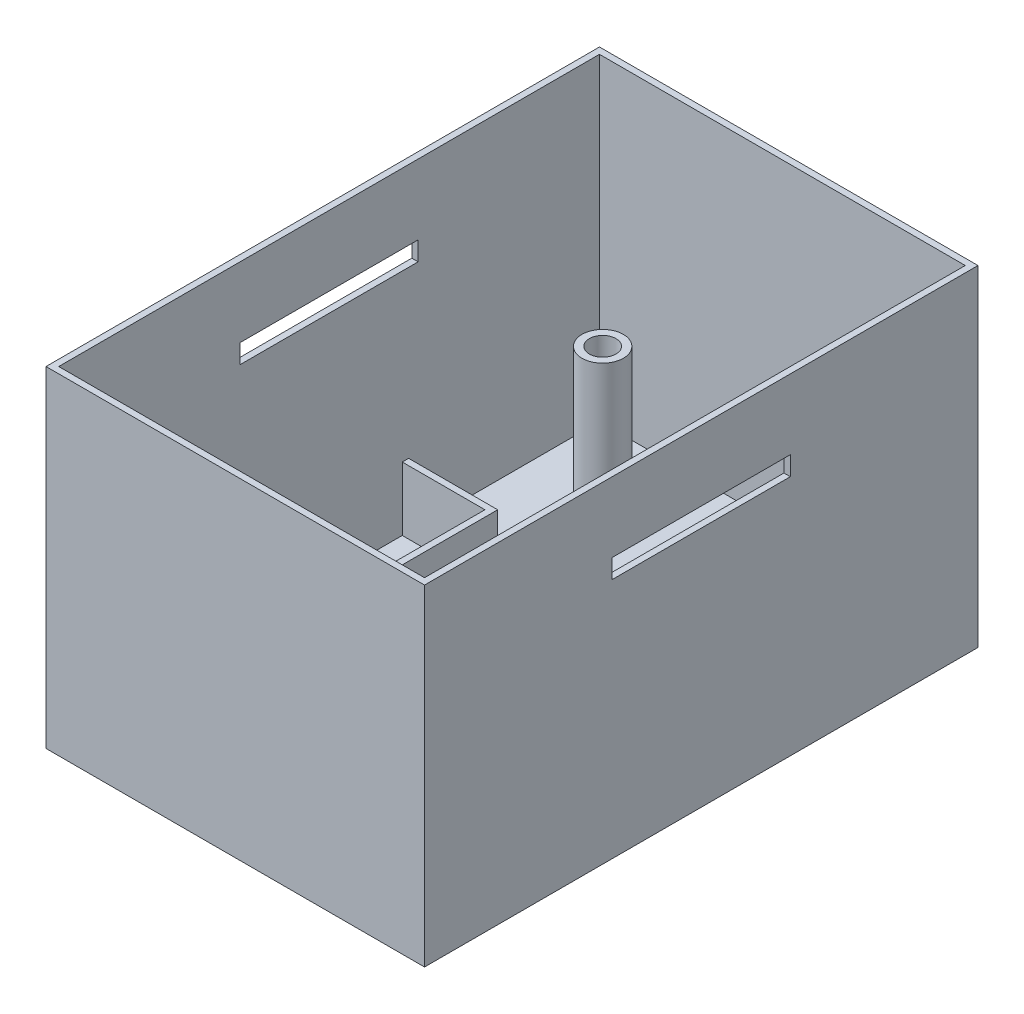
SolidWorks part; units mm, degrees
ref_plane "Alzado" through (0, 0, 0) normal (0, 0, 1) x (1, 0, 0)
ref_plane "Planta" through (0, 0, 0) normal (0, 1, 0) x (1, 0, 0)
ref_plane "Vista lateral" through (0, 0, 0) normal (1, 0, 0) x (0, 0, -1)
sketch "Croquis1" plane through (0, 0, 0) normal (0, 1, 0) x (1, 0, 0)
  line L0 (-19.25, 35.5) -> (-16.25, 35.5) construction
  line L1 (-19.25, -35.5) -> (19.25, -35.5) construction
  line L2 (-19.25, -35.5) -> (-19.25, 35.5) construction
  line L3 (-19.25, 35.5) -> (19.25, 35.5) construction
  line L4 (19.25, -35.5) -> (19.25, 35.5) construction
  line L5 (-19.25, -35.5) -> (19.25, 35.5) construction
  line L6 (-19.25, 35.5) -> (19.25, -35.5) construction
  line L7 (-28.75, -42.5) -> (28.75, -42.5)
  line L8 (-28.75, -42.5) -> (-28.75, 42.5)
  line L9 (-28.75, 42.5) -> (28.75, 42.5)
  line L10 (28.75, -42.5) -> (28.75, 42.5)
  line L11 (-28.75, -42.5) -> (28.75, 42.5) construction
  line L12 (-28.75, 42.5) -> (28.75, -42.5) construction
  line L13 (-19.25, 35.5) -> (-19.25, 32.5) construction
  line L14 (26.75, 41) -> (18.75, 41) construction
  line L15 (-26.75, -41) -> (26.75, -41) construction
  line L16 (-26.75, -41) -> (-26.75, 41) construction
  line L17 (0, 35.5) -> (0, -35.5) construction
  line L18 (0, -26.6301) -> (0, -35.5) construction
  line L19 (-28.75, -35.5) -> (-14.75, -35.5)
  line L20 (-14.75, -35.5) -> (-14.75, 12.5)
  line L21 (-14.75, 12.5) -> (-28.75, 12.5)
  line L22 (-15.75, -34.5) -> (-28.75, -34.5)
  line L23 (-15.75, -34.5) -> (-15.75, 11.5)
  line L24 (-15.75, 11.5) -> (-28.75, 11.5)
  line L25 (-29.75, -43.5) -> (-29.75, 43.5)
  line L26 (-29.75, 43.5) -> (29.75, 43.5)
  line L27 (29.75, -43.5) -> (29.75, 43.5)
  line L28 (-29.75, -43.5) -> (29.75, -43.5)
  line L29 (-28.75, -34.5) -> (-15.75, -34.5) construction
  line L30 (-26.75, 41) -> (26.75, 41) construction
  line L31 (26.75, -41) -> (26.75, 41) construction
  line L32 (-26.75, -41) -> (26.75, 41) construction
  line L33 (-26.75, 41) -> (26.75, -41) construction
  line L34 (18.75, 41) -> (18.75, 33) construction
  line L35 (26.75, -41) -> (19.75, -41) construction
  line L36 (19.75, -41) -> (19.75, -20) construction
  line L37 (-26.75, 41) -> (-18.75, 41) construction
  line L38 (-18.75, 41) -> (-18.75, 33) construction
  circle A2 centre (19.75, -20) radius 2.1
  circle A3 centre (19.75, -20) radius 3.25
  circle A4 centre (-18.75, 33) radius 2.1
  circle A5 centre (-18.75, 33) radius 3.25
  point P0 (0, 0)
  point P6 (0, 0)
  point P11 (0, 0)
  dimension "D7" = 8
  dimension "D8" = 8
  dimension "D13" = 8
  dimension "D14" = 4.2
  dimension "D15" = 21
  dimension "D19" = 4.2
  dimension "D20" = 6.5
  dimension "D22" = 6.5
  dimension "D1" = 71
  dimension "D2" = 38.5
  dimension "D3" = 57.5
  dimension "D4" = 85
  dimension "D5" = 53.5
  dimension "D6" = 82
  dimension "D9" = 8.8699
  dimension "D10" = 14
  dimension "D11" = 48
  dimension "D12" = 7
  dimension "D18" = 7
  dimension "D21" = 8
  dimension "D16" = 1
  dimension "D17" = 1
extrude "Saliente-Extruir1" add sketch "Croquis1" along normal blind 50 contours L25 L28 L27 L26 L10 L7 L8 L9 region at (-29.6446, 0, 0)
extrude "Saliente-Extruir2" add sketch "Croquis1<4>" along normal blind 10 contours L24 L23 L8 L19 L20 L21 region at (-28.25, 0, 35)
sketch "Croquis1<4>" plane through (0, 0, 0) normal (0, 1, 0) x (1, 0, 0) same geometry as "Croquis1"
extrude "Saliente-Extruir3" add sketch "Croquis1<5>" along normal blind 20 separate body contours A4 | A2 | A3 | A5 region at (19.75, 0, 20) region at (-18.75, 0, -33)
sketch "Croquis1<5>" plane through (0, 0, 0) normal (0, 1, 0) x (1, 0, 0) same geometry as "Croquis1"
sketch "Croquis2" plane through (0, 0, 0) normal (0, -1, 0) x (1, 0, 0)
  line L1 (-29.75, 43.5) -> (29.75, 43.5)
  line L2 (-29.75, 43.5) -> (-29.75, -43.5)
  line L3 (-29.75, -43.5) -> (29.75, -43.5)
  line L4 (29.75, 43.5) -> (29.75, -43.5)
extrude "Saliente-Extruir6" add sketch "Croquis2" along normal blind 2 contours L2 L1 L4 L3
sketch "Croquis5" plane through (0, -2, 0) normal (0, -1, 0) x (1, 0, 0)
  line L0 (-29.75, 0) -> (29.75, 0) construction
  line L1 (-29.75, 43.5) -> (-29.75, -43.5) construction
  line L2 (29.75, 43.5) -> (29.75, -43.5) construction
  line L3 (0, -43.5) -> (0, 43.5) construction
  line L4 (-29.75, -43.5) -> (29.75, -43.5) construction
  line L5 (-29.75, 43.5) -> (29.75, 43.5) construction
  line L6 (-29.75, 0) -> (-29.75, 23)
  line L7 (-29.75, 23) -> (-24.75, 23)
  line L8 (-24.75, 23) -> (-24.75, -23)
  line L9 (-24.75, -23) -> (-29.75, -23)
  line L10 (-29.75, -23) -> (-29.75, 0)
  line L11 (24.75, -23) -> (29.75, -23)
  line L12 (24.75, 23) -> (24.75, -23)
  line L13 (29.75, 23) -> (24.75, 23)
  line L14 (29.75, 0) -> (29.75, 23)
  line L15 (29.75, -23) -> (29.75, 0)
  dimension "D1" = 23
  dimension "D2" = 5
  dimension "D3" = 46
sketch "Croquis9" plane through (0, 0, 0) normal (0, 1, 0) x (1, 0, 0)
  circle A0 centre (-18.75, 33) radius 2.1
  circle A1 centre (19.75, -20) radius 2.1
extrude "Cortar-Extruir3" cut sketch "Croquis9" against normal blind 10
sketch "Croquis10" plane through (-29.75, 0, 0) normal (-1, 0, 0) x (0, 0, 1)
  line L0 (-43.5, 50) -> (43.5, 50) construction
  line L1 (43.5, 50) -> (43.5, -2) construction
  line L2 (43.5, -2) -> (-43.5, -2) construction
  line L3 (-43.5, -2) -> (43.5, -2) construction
  line L4 (-43.5, 50) -> (-43.5, -2) construction
  line L5 (-43.5, -2) -> (-43.5, 50) construction
  line L6 (0, 50) -> (0, 39) construction
  line L7 (0, 39) -> (14, 39)
  line L8 (14, 39) -> (14, 36)
  line L9 (14, 36) -> (-14, 36)
  line L10 (-14, 36) -> (-14, 39)
  line L11 (-14, 39) -> (0, 39)
  dimension "D1" = 11
  dimension "D2" = 3
  dimension "D3" = 14
  dimension "D4" = 14
extrude "Cortar-Extruir4" cut sketch "Croquis10" against normal blind 100
